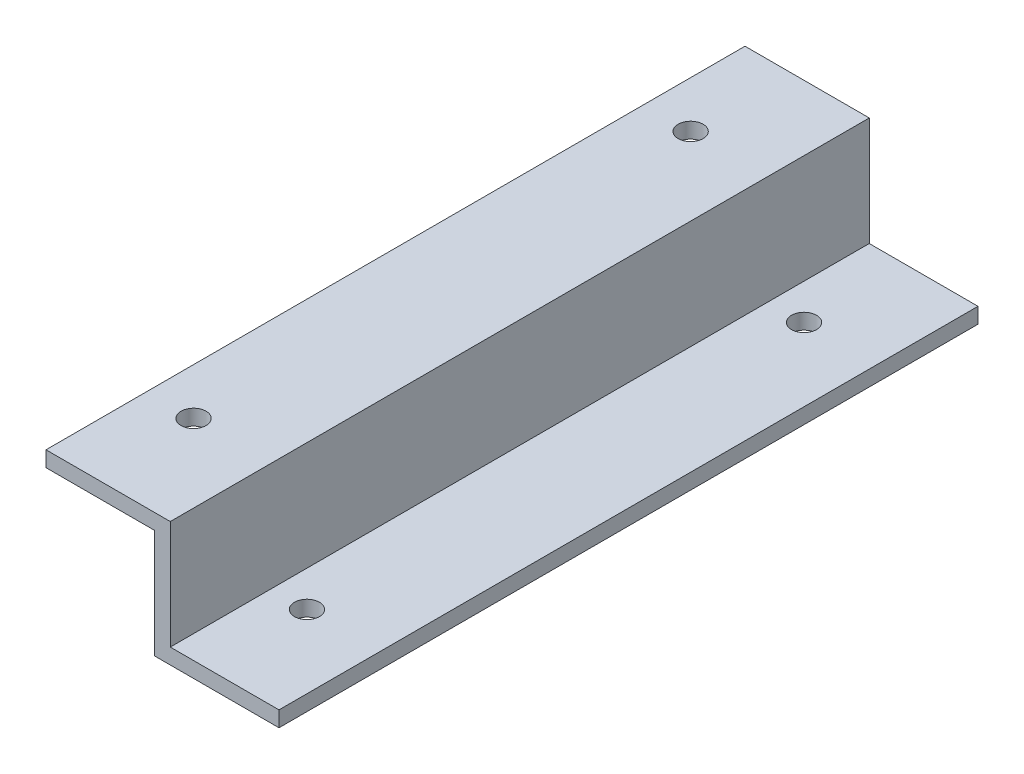
SolidWorks part; units mm, degrees
ref_plane "Front Plane" through (0, 0, 0) normal (0, 0, 1) x (1, 0, 0)
ref_plane "Top Plane" through (0, 0, 0) normal (0, 1, 0) x (1, 0, 0)
ref_plane "Right Plane" through (0, 0, 0) normal (1, 0, 0) x (0, 0, -1)
sketch "Sketch1" plane through (0, 0, 0) normal (0, 0, 1) x (1, 0, 0)
  line L0 (0, -11.1125) -> (0, 11.1125) construction
  line L1 (0, 11.1125) -> (-23.8125, 11.1125) construction
  line L2 (0, -11.1125) -> (23.8125, -11.1125) construction
  line L3 (1.5875, -9.525) -> (23.8125, -9.525) construction
  line L4 (1.5875, -9.525) -> (1.5875, 12.7) construction
  line L5 (1.5875, 12.7) -> (-23.8125, 12.7) construction
  line L6 (-1.5875, -12.7) -> (23.8125, -12.7) construction
  line L7 (-1.5875, -12.7) -> (-1.5875, 9.525) construction
  line L8 (-1.5875, 9.525) -> (-23.8125, 9.525) construction
  line L9 (-23.8125, 12.7) -> (-23.8125, 9.525) construction
  line L10 (23.8125, -9.525) -> (23.8125, -12.7) construction
  point P4 (0, 0)
  dimension "Leg Width" = 25.4
  dimension "Outside Height" = 25.4
  dimension "Wall Thickness" = 3.175
sketch "Sketch2" plane through (0, 0, 0) normal (1, 0, 0) x (0, 0, -1)
  line L0 (71.4375, 0) -> (-71.4375, 0) construction
  line L1 (0, 0) -> (0, 12.7) construction
  line L2 (-71.4375, 0) -> (-71.4375, 12.7) construction
  line L3 (71.4375, 0) -> (71.4375, 12.7) construction
  point P0 (-53.5781, 0)
  point P3 (53.5781, 0)
  point P4 (0, 0)
  dimension "D1" = 107.1562
  dimension "Length" = 142.875
sketch "Sketch3" plane through (0, 0, 0) normal (0, 0, 1) x (1, 0, 0)
  line L0 (23.8125, -9.525) -> (23.8125, -12.7) construction
  line L1 (1.5875, -9.525) -> (23.8125, -9.525) construction
  line L2 (-1.5875, -12.7) -> (23.8125, -12.7) construction
  line L3 (-1.5875, -12.7) -> (-1.5875, 9.525) construction
  line L4 (1.5875, -9.525) -> (1.5875, 12.7) construction
  line L5 (1.5875, 12.7) -> (-23.8125, 12.7) construction
  line L6 (-23.8125, 12.7) -> (-23.8125, 9.525) construction
  line L7 (-1.5875, 9.525) -> (-23.8125, 9.525) construction
  line L8 (23.8125, -9.525) -> (23.8125, -12.7)
  line L9 (1.5875, -9.525) -> (23.8125, -9.525)
  line L10 (-1.5875, -12.7) -> (23.8125, -12.7)
  line L11 (-1.5875, -12.7) -> (-1.5875, 9.525)
  line L12 (1.5875, -9.525) -> (1.5875, 12.7)
  line L13 (1.5875, 12.7) -> (-23.8125, 12.7)
  line L14 (-23.8125, 12.7) -> (-23.8125, 9.525)
  line L15 (-1.5875, 9.525) -> (-23.8125, 9.525)
extrude "Boss-Extrude1" add sketch "Sketch3" along normal up to vertex (71.4375 mm away) and the other way up to vertex (71.4375 mm away) up to point (0, 0, 71.4375) other way up to point (0, 0, -71.4375)
hole_wizard "#10 Clearance Hole1" positions "Sketch4" profile "Sketch5" hole size "#10" standard "ANSI Inch" end condition through all
sketch "Sketch4" plane through (0, 12.7, 0) normal (0, 1, 0) x (1, 0, 0)
  point P0 (-14.2875, -50.8003)
  point P3 (-14.2875, 50.7997)
sketch "Sketch5" plane through (-14.2875, 12.7, 50.8003) normal (1, 0, 0) x (0, 0, 1)
  line L0 (0, 0) -> (0, 25.4)
  line L1 (0, 25.4) -> (2.5527, 25.4)
  line L2 (2.5527, 25.4) -> (2.5527, 0)
  line L5 (2.5527, 0) -> (0, 0)
  line L11 (0, -6.35) -> (0, 107.95) construction
  dimension "Thru Hole Dia." = 5.1054
  dimension "Thru Hole Depth" = 25.4
sketch "Sketch7" plane through (0, -9.525, 0) normal (0, 1, 0) x (1, 0, 0)
  line L0 (-14.2875, -50.8003) -> (8.89, -50.8003) construction
  line L1 (8.89, -50.8003) -> (8.89, 50.7997) construction
hole_wizard "#10 Clearance Hole2" positions "Sketch8" profile "Sketch9" hole size "#10" standard "ANSI Inch" end condition through all
sketch "Sketch8" plane through (0, -9.525, 0) normal (0, 1, 0) x (1, 0, 0)
  point P0 (8.89, -50.8003)
  point P3 (8.89, 50.7997)
sketch "Sketch9" plane through (8.89, -9.525, 50.8003) normal (1, 0, 0) x (0, 0, 1)
  line L0 (0, 0) -> (0, 3.175)
  line L1 (0, 3.175) -> (2.5527, 3.175)
  line L2 (2.5527, 3.175) -> (2.5527, 0)
  line L5 (2.5527, 0) -> (0, 0)
  line L11 (0, -6.35) -> (0, 107.95) construction
  dimension "Thru Hole Dia." = 5.1054
  dimension "Thru Hole Depth" = 3.175
equation "\"D1@Sketch2\"=\"Length@Sketch2\"*0.75"
